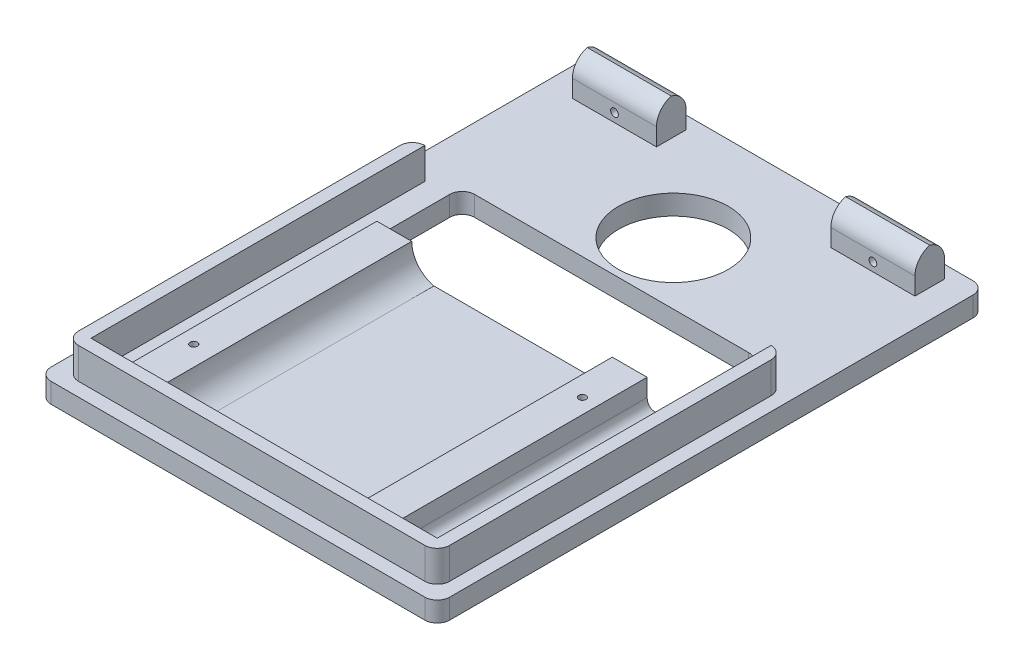
SolidWorks part; units mm, degrees
ref_plane "Front Plane" through (0, 0, 0) normal (0, 0, 1) x (1, 0, 0)
ref_plane "Top Plane" through (0, 0, 0) normal (0, 1, 0) x (1, 0, 0)
ref_plane "Right Plane" through (0, 0, 0) normal (1, 0, 0) x (0, 0, -1)
sketch "Sketch3" plane through (0, 0, 0) normal (0, 1, 0) x (1, 0, 0)
  line L0 (-75, 110) -> (75, 110)
  line L1 (-75, -105) -> (75, -105)
  line L2 (-75, -105) -> (-75, 105)
  line L4 (75, -105) -> (75, 105)
  line L5 (-75, -105) -> (75, 105) construction
  line L6 (-75, 105) -> (75, -105) construction
  line L7 (80, -105) -> (80, 105)
  line L8 (-75, -110) -> (75, -110)
  line L9 (-80, -105) -> (-80, 105)
  line L10 (-80, -110) -> (80, -110) construction
  line L11 (-80, -110) -> (-80, 110) construction
  line L12 (80, -110) -> (80, 110) construction
  line L13 (-80, 110) -> (80, 110) construction
  line L15 (-75, 105) -> (75, 105)
  line L19 (-75, 105) -> (75, 105) construction
  line L20 (-69.75, 104.9) -> (69.75, 104.9)
  line L21 (-69.75, 104.9) -> (-69.75, 93)
  line L22 (-69.75, 93) -> (69.75, 93)
  line L23 (69.75, 104.9) -> (69.75, 93)
  arc A0 (-75, -110) -> (-80, -105) centre (-75, -105) cw
  arc A1 (80, -105) -> (75, -110) centre (75, -105) cw
  arc A2 (75, 110) -> (80, 105) centre (75, 105) cw
  arc A3 (-75, 110) -> (-80, 105) centre (-75, 105) ccw
  point P0 (0, 0)
  point P5 (0, 93)
  dimension "D4" = 5
  dimension "D1" = 75
  dimension "D2" = 210
  dimension "D5" = 11.9
  dimension "D6" = 139.5
  dimension "D7" = 0.1
  dimension "D3" = 5
extrude "Boss-Extrude1" add sketch "Sketch3" along normal blind 8 contours L1 L4 L2 | L0 A3 L9 A0 L8 A1 L7 A2 L4 L1 L2 | L2 L4 | L23 L15 L21 L22 region at (0, 0, -107.2797) region at (0, 0, 5.5048) region at (0, 0, -98.95)
extrude "Boss-Extrude2" add sketch "Sketch3<7>" along normal blind 15 from surface contours L23 L15 L21 L22 region at (0, 0, -98.95) starting at face at (0, 8, 0)
sketch "Sketch3<7>" plane through (0, 0, 0) normal (0, 1, 0) x (1, 0, 0) same geometry as "Sketch3"
fillet "Fillet1" radius 8 2 edges at (0, 23, -93) (0, 23, -104.9)
sketch "Sketch4" plane through (0, 0, 0) normal (0, -1, 0) x (1, 0, 0)
  line L1 (-55, 0) -> (55, 0)
  line L2 (-60, -5) -> (-60, -35)
  line L3 (-55, -40) -> (55, -40)
  line L4 (60, -5) -> (60, -35)
  line L5 (-75, 110) -> (75, 110) construction
  line L6 (80, 105) -> (80, -105) construction
  line L7 (-75, -110) -> (75, -110) construction
  arc A0 (-55, 0) -> (-60, -5) centre (-55, -5) ccw
  arc A1 (-60, -35) -> (-55, -40) centre (-55, -35) ccw
  arc A2 (55, -40) -> (60, -35) centre (55, -35) ccw
  arc A3 (55, 0) -> (60, -5) centre (55, -5) cw
  point P4 (0, -40)
  dimension "D4" = 5
  dimension "D1" = 70
  dimension "D2" = 110
  dimension "D3" = 20
extrude "Cut-Extrude1" cut sketch "Sketch4" against normal up to next
sketch "Sketch5" plane through (0, 8, 0) normal (0, 1, 0) x (1, 0, 0)
  line L0 (75, -105) -> (75, 105) construction
  line L1 (-75, -105) -> (75, -105) construction
  line L2 (-75, -105) -> (-75, 105) construction
  line L3 (-75, 105) -> (75, 105) construction
  line L4 (75, 110) -> (-75, 110)
  line L5 (80, -105) -> (80, 105)
  line L6 (-75, -110) -> (75, -110)
  line L7 (-80, 105) -> (-80, -105)
  line L8 (75, 110) -> (-75, 110)
  line L9 (80, -105) -> (80, 105)
  line L10 (-75, -110) -> (75, -110)
  line L11 (-80, 105) -> (-80, -105)
  line L12 (69.75, 104.9) -> (-69.75, 104.9)
  line L13 (-69.75, 104.9) -> (-69.75, 93)
  line L14 (-69.75, 93) -> (69.75, 93)
  line L15 (69.75, 93) -> (69.75, 104.9)
  line L16 (69.75, 104.9) -> (-69.75, 104.9)
  line L17 (-69.75, 104.9) -> (-69.75, 93)
  line L18 (-69.75, 93) -> (69.75, 93)
  line L19 (69.75, 93) -> (69.75, 104.9)
  line L20 (75, -105) -> (75, 105)
  line L21 (-75, -105) -> (75, -105)
  line L22 (-75, -105) -> (-75, 105)
  line L23 (-75, 105) -> (75, 105)
  line L24 (-75, 35) -> (75, 35)
  line L25 (-69.5, 34.5) -> (-69.5, -99.5)
  line L26 (-69.5, -104.5) -> (69.5, -104.5)
  line L27 (-74.5, -99.5) -> (-74.5, 29.5)
  line L28 (-69.5, 34.5) -> (69.5, 34.5)
  line L29 (74.5, -99.5) -> (74.5, 29.5)
  line L30 (-69.5, -99.5) -> (69.5, -99.5)
  line L31 (69.5, -99.5) -> (69.5, 34.5)
  arc A0 (-74.5, 29.5) -> (-69.5, 34.5) centre (-69.5, 29.5) cw
  arc A1 (69.5, 34.5) -> (74.5, 29.5) centre (69.5, 29.5) cw
  arc A2 (69.5, -104.5) -> (74.5, -99.5) centre (69.5, -99.5) ccw
  arc A3 (-69.5, -104.5) -> (-74.5, -99.5) centre (-69.5, -99.5) cw
  arc A4 (80, 105) -> (75, 110) centre (75, 105) ccw
  arc A5 (75, -110) -> (80, -105) centre (75, -105) ccw
  arc A6 (-80, -105) -> (-75, -110) centre (-75, -105) ccw
  arc A7 (-75, 110) -> (-80, 105) centre (-75, 105) ccw
  arc A8 (80, 105) -> (75, 110) centre (75, 105) ccw
  arc A9 (75, -110) -> (80, -105) centre (75, -105) ccw
  arc A10 (-80, -105) -> (-75, -110) centre (-75, -105) ccw
  arc A11 (-75, 110) -> (-80, 105) centre (-75, 105) ccw
  point P26 (0, -104.5)
  point P42 (0, -99.5)
  dimension "D7" = 5
  dimension "D3" = 75
  dimension "D4" = 0.5
  dimension "D5" = 0.5
  dimension "D6" = 0.5
  dimension "D8" = 5
  dimension "D9" = 5
  dimension "D1" = 0
  dimension "D2" = 0
extrude "Boss-Extrude3" add sketch "Sketch5" along normal blind 12.5 contours A3 L26 A2 L29 A1 L31 L30 L25 A0 L27 region at (-71.5377, 8, 32.5)
sketch "Sketch8" plane through (0, 0, 99.5) normal (0, 0, -1) x (-1, 0, 0)
  line L0 (-28.95, 19.05) -> (28.95, 19.05) construction
  line L1 (-28.95, 30.1) -> (28.95, 30.1)
  line L2 (-28.95, 8) -> (28.95, 8)
  line L3 (69.5, 8) -> (-69.5, 8) construction
  line L4 (0, 19.05) -> (0, 0) construction
  line L5 (-28.95, 30.35) -> (28.95, 30.35)
  line L6 (-28.95, 7.75) -> (28.95, 7.75)
  line L7 (-28.95, 33.35) -> (28.95, 33.35)
  line L8 (-28.95, 4.75) -> (28.95, 4.75)
  line L9 (-38.0268, 8) -> (38.0268, 8)
  line L10 (-43.25, 19.05) -> (43.25, 19.05)
  line L11 (-28.95, 4.75) -> (-54.25, 4.75)
  line L12 (-54.25, 4.75) -> (-54.25, 19.05)
  line L13 (-54.25, 19.05) -> (-43.25, 19.05)
  line L14 (54.25, 19.05) -> (43.25, 19.05)
  line L15 (28.95, 4.75) -> (54.25, 4.75)
  line L16 (54.25, 4.75) -> (54.25, 19.05)
  line L18 (-54.25, 19.05) -> (-54.0716, 19.05)
  line L19 (-54.0716, 19.05) -> (-54.0716, 21.05)
  line L20 (-54.0716, 21.05) -> (-40.0716, 21.05)
  line L21 (54.0716, 21.05) -> (40.0716, 21.05)
  line L22 (54.0716, 19.05) -> (54.0716, 21.05)
  line L23 (54.25, 19.05) -> (54.0716, 19.05)
  arc A0 (-28.95, 30.1) -> (-28.95, 8) centre (-28.95, 19.05) ccw
  arc A1 (28.95, 8) -> (28.95, 30.1) centre (28.95, 19.05) ccw
  arc A2 (28.95, 7.75) -> (28.95, 30.35) centre (28.95, 19.05) ccw
  arc A3 (-28.95, 30.35) -> (-28.95, 7.75) centre (-28.95, 19.05) ccw
  arc A4 (28.95, 4.75) -> (28.95, 33.35) centre (28.95, 19.05) ccw
  arc A5 (-28.95, 33.35) -> (-28.95, 4.75) centre (-28.95, 19.05) ccw
  point P2 (0, 19.05)
  point P29 (0, 19.05)
  line M6 (-69.5, 8) -> (69.5, 8)
  line M8 (69.5, 20.5) -> (-69.5, 20.5)
  dimension "D2" = 80
  dimension "D5" = 14
  dimension "D1" = 22.1
  dimension "D6" = 14
  dimension "D7" = 2
  dimension "D3" = 0.25
  dimension "D4" = 3
extrude "Boss-Extrude4" add sketch "Sketch8" along normal up to surface (99.5 mm away) contours L9 A4 A2 M8 | A5 A3 M8 M6 | A4 L16 L14 M6 | A5 L13 L12 M6 region at (39.4137, 12.9121, 99.5) region at (-39.4137, 12.9121, 99.5) region at (47.8657, 13.1621, 99.5) region at (-47.8657, 13.1621, 99.5) up to face at (0, 4, 0)
sketch "Sketch9" plane through (0, 8, 0) normal (0, 1, 0) x (1, 0, 0)
  line L0 (69.75, 98.95) -> (-69.75, 98.95) construction
  line L1 (-35, 104.9) -> (35, 104.9)
  line L2 (-35, 104.9) -> (-35, 93)
  line L3 (-35, 93) -> (35, 93)
  line L4 (35, 104.9) -> (35, 93)
  line L5 (-35, 104.9) -> (35, 93) construction
  line L6 (-35, 93) -> (35, 104.9) construction
  line L7 (69.75, 93) -> (-69.75, 93) construction
  line L9 (-69.75, 104.9) -> (-68.75, 104.9)
  line L10 (-69.75, 104.9) -> (-69.75, 93)
  line L11 (-69.75, 93) -> (-68.75, 93)
  line L12 (-68.75, 104.9) -> (-68.75, 93)
  line L13 (69.75, 104.9) -> (68.75, 104.9)
  line L14 (69.75, 104.9) -> (69.75, 93)
  line L15 (69.75, 93) -> (68.75, 93)
  line L16 (68.75, 104.9) -> (68.75, 93)
  point P0 (0, 98.95)
  dimension "D1" = 70
  dimension "D2" = 1
extrude "Cut-Extrude3" cut sketch "Sketch9" along normal up to next
sketch "Sketch11" plane through (0, 0, 0) normal (0, -1, 0) x (1, 0, 0)
  circle A0 centre (0, -64.78) radius 22
  dimension "D1" = 44
extrude "Cut-Extrude5" cut sketch "Sketch11" against normal up to next
fillet "Fillet2" radius 4 2 edges at (54.25, 8, 49.75) (-54.25, 8, 49.75)
sketch "Sketch12" plane through (0, 19.05, 0) normal (0, 1, 0) x (1, 0, 0)
  line L0 (40.25, 0) -> (54.25, 0) construction
  line L1 (-69.5, -99.5) -> (69.5, -99.5) construction
  line L4 (40.25, 0) -> (40.25, -99.5) construction
  line L5 (-40.25, 0) -> (-40.25, -99.5) construction
  circle A0 centre (48.25, -20) radius 1.45
  circle A1 centre (-48.25, -79.5) radius 1.45
  dimension "D1" = 2.9
  dimension "D4" = 8
  dimension "D5" = 8
  dimension "D2" = 20
  dimension "D3" = 20
extrude "Cut-Extrude6" cut sketch "Sketch12" against normal up to next
sketch "Sketch13" plane through (0, 0, 0) normal (0, -1, 0) x (1, 0, 0)
  circle A0 centre (-48.25, 79.5) radius 4
  circle A1 centre (48.25, 20) radius 4
  dimension "D1" = 8
extrude "Cut-Extrude7" cut sketch "Sketch13" against normal blind 4
sketch "Sketch6" plane through (0, 0, -104.9) normal (0, 0, -1) x (-1, 0, 0)
  line L1 (0, 0) -> (0, 22.7329) construction
  line L3 (-68.75, 8) -> (-35, 8) construction
  line L4 (75, 0) -> (-75, 0) construction
  line L5 (-68.75, 15) -> (-68.75, 8) construction
  circle A0 centre (-51.875, 11.5) radius 1.55
  circle A1 centre (51.875, 11.5) radius 1.55
  point P3 (0, 0)
  point P14 (-51.875, 8)
  point P17 (0, 0)
  point P21 (-68.75, 11.5)
  dimension "D1" = 3.1
extrude "Cut-Extrude2" cut sketch "Sketch6" against normal up to next
